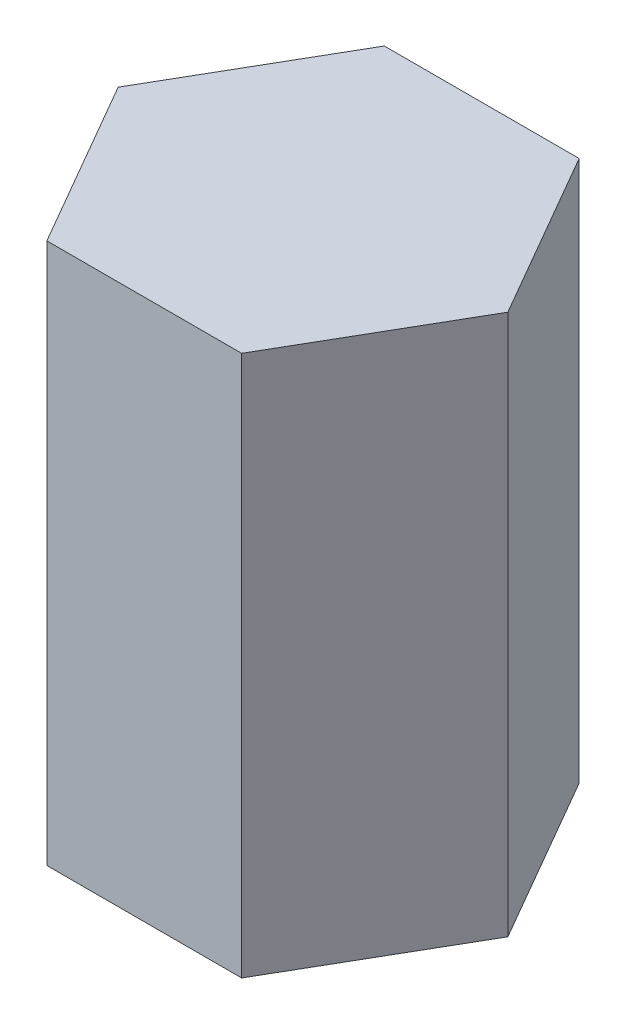
SolidWorks part; units mm, degrees
material "Bus"
ref_plane "Front Plane" through (0, 0, 0) normal (0, 0, 1) x (1, 0, 0)
ref_plane "Top Plane" through (0, 0, 0) normal (0, 1, 0) x (1, 0, 0)
ref_plane "Right Plane" through (0, 0, 0) normal (1, 0, 0) x (0, 0, -1)
sketch "Sketch2" plane through (0, 0, 0) normal (0, 1, 0) x (1, 0, 0)
  line L1 (577.3503, 0) -> (288.6751, 500)
  line L2 (288.6751, 500) -> (-288.6751, 500)
  line L3 (-288.6751, 500) -> (-577.3503, 0)
  line L4 (-577.3503, 0) -> (-288.6751, -500)
  line L5 (-288.6751, -500) -> (288.6751, -500)
  line L6 (288.6751, -500) -> (577.3503, 0)
  circle A0 centre (0, 0) radius 500 construction
  dimension "D1" = 1000
extrude "Boss-Extrude1" add sketch "Sketch2" along normal blind 1603
ref_axis "Axis1" through (0, -313.0569, 0) along (0, 1, 0)
ref_plane "Plane2" through (0, 400.75, 0) normal (0, 1, 0) x (1, 0, 0)
sketch "Sketch3" plane through (0, 400.75, 0) normal (0, 1, 0) x (1, 0, 0)
  line L0 (288.6751, 500) -> (-288.6751, 500) construction
  line L1 (560.0298, 0) -> (280.0149, 485)
  line L2 (280.0149, 485) -> (-280.0149, 485)
  line L3 (-280.0149, 485) -> (-560.0298, 0)
  line L4 (-560.0298, 0) -> (-280.0149, -485)
  line L5 (-280.0149, -485) -> (280.0149, -485)
  line L6 (280.0149, -485) -> (560.0298, 0)
  circle A0 centre (0, 0) radius 485 construction
  dimension "D1" = 970
extrude "Cut-Extrude1" cut sketch "Sketch3" along normal blind 1187.25
